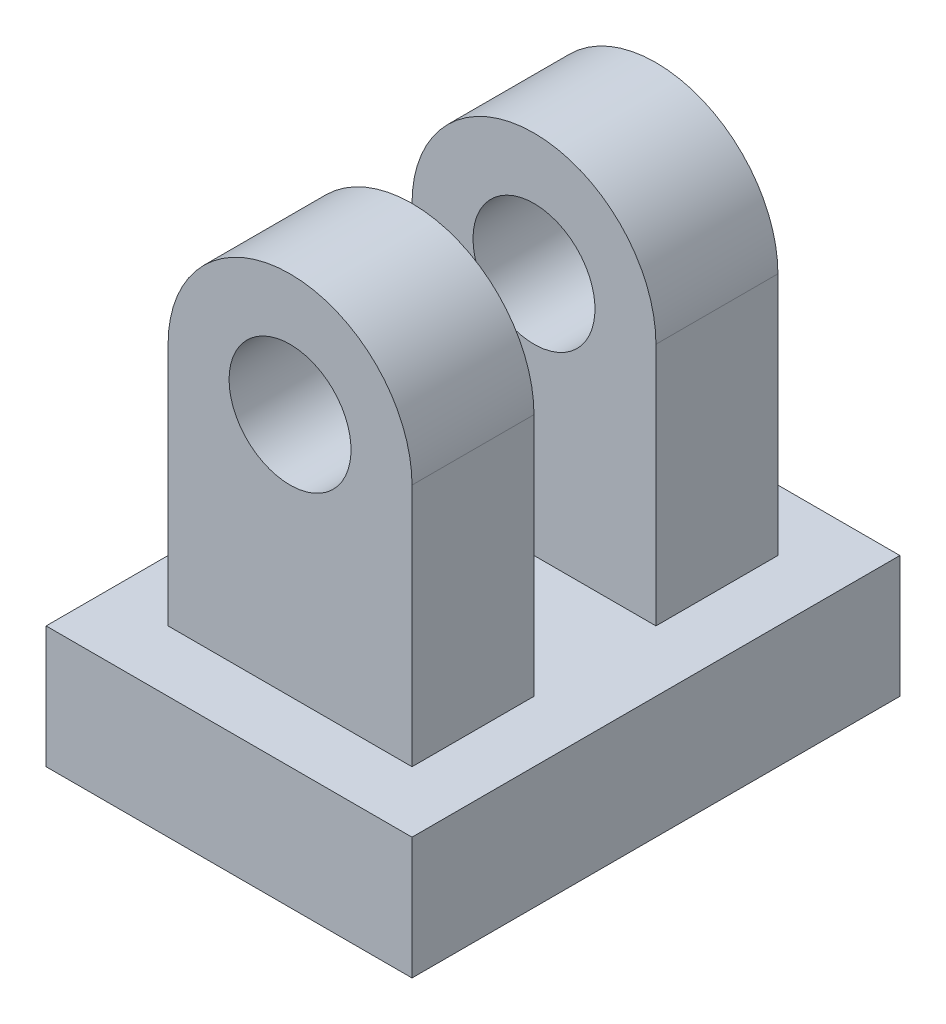
SolidWorks part; units mm, degrees
ref_plane "Front Plane" through (0, 0, 0) normal (0, 0, 1) x (1, 0, 0)
ref_plane "Top Plane" through (0, 0, 0) normal (0, 1, 0) x (1, 0, 0)
ref_plane "Right Plane" through (0, 0, 0) normal (1, 0, 0) x (0, 0, -1)
sketch "Sketch1" plane through (0, 0, 0) normal (0, 1, 0) x (1, 0, 0)
  line L1 (-1.5, 2) -> (1.5, 2)
  line L2 (-1.5, 2) -> (-1.5, -2)
  line L3 (-1.5, -2) -> (1.5, -2)
  line L4 (1.5, 2) -> (1.5, -2)
  line L5 (-1.5, 2) -> (1.5, -2) construction
  line L6 (-1.5, -2) -> (1.5, 2) construction
  line L7 (-1, 1.5) -> (1, 1.5)
  line L8 (-1, 1.5) -> (-1, 0.5)
  line L9 (-1, 0.5) -> (1, 0.5)
  line L10 (1, 1.5) -> (1, 0.5)
  line L11 (-1, 1.5) -> (1, 0.5) construction
  line L12 (-1, 0.5) -> (1, 1.5) construction
  line L13 (-1, -0.5) -> (1, -0.5)
  line L14 (-1, -0.5) -> (-1, -1.5)
  line L15 (-1, -1.5) -> (1, -1.5)
  line L16 (1, -0.5) -> (1, -1.5)
  line L17 (-1, -0.5) -> (1, -1.5) construction
  line L18 (-1, -1.5) -> (1, -0.5) construction
  point P0 (0, 0)
  point P6 (0, 1)
  point P11 (0, -1)
  point P16 (-0.0932, 1.4068)
  point P17 (0, 0)
  point P18 (0, 0)
  point P19 (-1.2915, 0.7085)
  point P20 (0.9129, -1.5409)
  point P21 (0, 0)
  point P22 (0, 0)
  point P23 (-1.4737, -1.4737)
  point P24 (0.2018, 1.2018)
  point P25 (0.6648, 1.6648)
  point P26 (0, 0)
  point P27 (0, 0)
  point P28 (0.7052, 1.7052)
  point P29 (0, 0)
  point P30 (0, 0)
  point P31 (0.7108, 0.7108)
  point P32 (0, 0)
  point P33 (1.0567, 0.6525)
  point P34 (0.0567, 1.1525)
  point P35 (0, 0)
  point P36 (-0.2917, 1.1739)
  point P37 (0.2027, 0.9492)
  point P38 (0, 0)
  dimension "D1" = 3
  dimension "D2" = 4
  dimension "D3" = 2
  dimension "D4" = 2
  dimension "D5" = 1
  dimension "D6" = 1
  dimension "D7" = 0.5
  dimension "D8" = 0.5
extrude "Boss-Extrude1" add sketch "Sketch1" against normal blind 1 contours L4 L1 L2 L3 L7 L10 L9 L8 L13 L16 L15 L14 | L16 L13 L14 L15 | L10 L7 L8 L9 region at (0, 0, 0) region at (0, 0, -1) region at (0, 0, 1)
extrude "Boss-Extrude2" add sketch "Sketch1<3>" along normal blind 3 contours L16 L13 L14 L15 | L10 L7 L8 L9 region at (0, 0, -1) region at (0, 0, 1)
sketch "Sketch1<3>" plane through (0, 0, 0) normal (0, 1, 0) x (1, 0, 0) same geometry as "Sketch1"
sketch "Sketch2" plane through (0, 0, -1.5) normal (0, 0, -1) x (-1, 0, 0)
  line L0 (1, 3) -> (-1, 3) construction
  line L1 (-1, 3) -> (-1, 0) construction
  line L6 (-1, 0) -> (1, 0)
  line L7 (1, 0) -> (1, 3)
  line L8 (1, 3) -> (-1, 3)
  line L9 (-1, 3) -> (-1, 0)
  line L10 (-1, 0) -> (1, 0)
  line L11 (1, 0) -> (1, 3)
  line L12 (1, 3) -> (-1, 3)
  line L13 (-1, 3) -> (-1, 0)
  circle A0 centre (0, 2) radius 1
  circle A1 centre (0, 2) radius 0.5
  line M7 (1, 3) -> (-1, 3)
  line M8 (-1, 3) -> (-1, 0)
  dimension "D1" = 2
  dimension "D3" = 1
  dimension "D2" = 0
extrude "Cut-Extrude1" cut sketch "Sketch2" against normal blind 3 contours A0 L12 M8 | A0 L11 M7 | A1 region at (0.7766, 2.7766, -1.5) region at (-0.7766, 2.7766, -1.5) region at (0, 2, -1.5)
